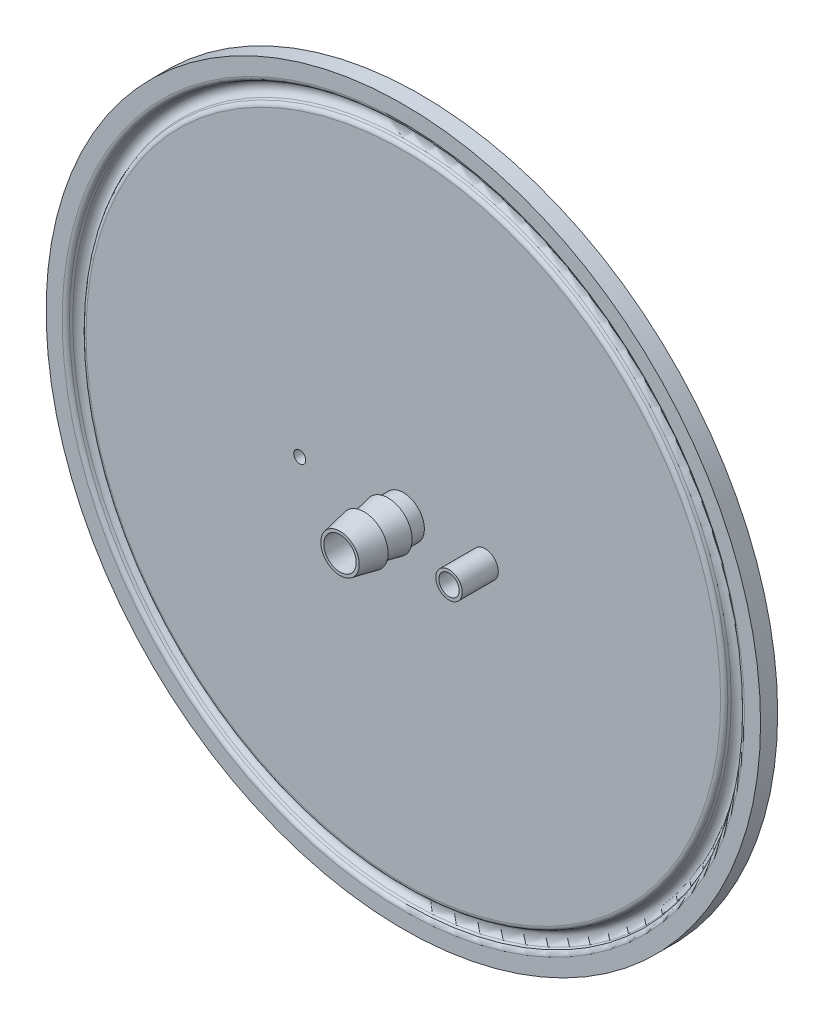
SolidWorks part; units mm, degrees
ref_plane "Front Plane" through (0, 0, 0) normal (0, 0, 1) x (1, 0, 0)
ref_plane "Top Plane" through (0, 0, 0) normal (0, 1, 0) x (1, 0, 0)
ref_plane "Right Plane" through (0, 0, 0) normal (1, 0, 0) x (0, 0, -1)
sketch "Sketch1" plane through (0, 0, 0) normal (1, 0, 0) x (0, 0, -1)
  line L0 (0, 0) -> (7.9248, 0) construction
  line L1 (0, 0) -> (0, 52.8099)
  line L2 (0, 59.4614) -> (2.8448, 59.4614)
  line L3 (2.8448, 59.4614) -> (7.9248, 45.5042)
  line L4 (7.9248, 45.5042) -> (7.9248, 0)
  line L5 (0, 56.7911) -> (0, 59.4614)
  line L6 (0.4797, 56.0663) -> (0.8729, 55.8994)
  line L7 (0.4797, 53.5347) -> (0.8729, 53.7016)
  line L8 (0, 56.2699) -> (0, 53.3311) construction
  line L9 (0, 54.8005) -> (0.4064, 54.8005) construction
  line L10 (0, 0) -> (7.9248, 0)
  arc A0 (0.8729, 53.7016) -> (0.8729, 55.8994) centre (0.4064, 54.8005) ccw
  arc A2 (0, 52.8099) -> (0.4797, 53.5347) centre (0.7874, 52.8099) cw
  arc A3 (0, 56.7911) -> (0.4797, 56.0663) centre (0.7874, 56.7911) ccw
  dimension "K" = 1.1938
  dimension "L" = 0.7874
  dimension "I" = 20
  dimension "C" = 91.0084
  dimension "F" = 2.8448
  dimension "H" = 0.4064
  dimension "B" = 109.601
  dimension "A" = 118.9228
  dimension "M" = 46
  dimension "N" = 23
  dimension "Length" = 7.9248
revolve "Revolve1" add sketch "Sketch1" angle 360 about L0
sketch "Sketch2" plane through (0, 0, -7.9248) normal (0, 0, -1) x (-1, 0, 0)
  circle A0 centre (-13.6038, 0) radius 2.2
  circle A1 centre (-13.6038, 0) radius 1.7
  dimension "D1" = 4.4
  dimension "D2" = 3.4
extrude "Boss-Extrude1" add sketch "Sketch2" along normal blind 6 separate body
sketch "Sketch3" plane through (0, 0, -7.9248) normal (0, 0, -1) x (-1, 0, 0)
  circle A0 centre (0, 0) radius 3.5
  dimension "D1" = 7
extrude "Boss-Extrude2" add sketch "Sketch3" along normal blind 2.54 separate body contours A0
sketch "Sketch4" plane through (0, 0, -10.4648) normal (0, 0, -1) x (-1, 0, 0)
  circle A0 centre (0, 0) radius 4
  dimension "D1" = 8
ref_plane "Plane1" through (0, 0, -14.4648) normal (0, 0, -1) x (-1, 0, 0)
sketch "Sketch6" plane through (0, 0, -14.4648) normal (0, 0, -1) x (-1, 0, 0)
  circle A0 centre (0, 0) radius 3.2
  dimension "D1" = 6.4
loft "Loft1" add profiles "Sketch6", "Sketch4" connector at (1.934, -2.5495, -14.4648) connector at (3.0203, -2.6225, -10.4648)
ref_plane "Plane2" through (0, 0, -18.4648) normal (0, 0, -1) x (-1, 0, 0)
sketch "Sketch7" plane through (0, 0, -14.4648) normal (0, 0, -1) x (-1, 0, 0)
  circle A0 centre (0, 0) radius 4
  dimension "D1" = 8
sketch "Sketch9" plane through (0, 0, -18.4648) normal (0, 0, -1) x (-1, 0, 0)
  circle A0 centre (0, 0) radius 3.2
  dimension "D1" = 6.4
loft "Loft2" add profiles "Sketch9", "Sketch7" connector at (3.1438, 0.5969, -18.4648) connector at (3.5954, 1.753, -14.4648)
ref_plane "Plane3" through (0, 0, -3.9624) normal (0, 0, -1) x (-1, 0, 0)
mirror "Mirror1" about plane through (0, 0, -3.9624) normal (0, 0, -1) of bodies 108 112
sketch "Sketch10" plane through (0, 0, -18.4648) normal (0, 0, -1) x (-1, 0, 0)
  circle A0 centre (0, 0) radius 2.7
  dimension "D1" = 5.4
extrude "Cut-Extrude1" cut sketch "Sketch10" against normal through all
sketch "Sketch11" plane through (0, 0, -7.9248) normal (0, 0, -1) x (-1, 0, 0)
  circle A0 centre (-13.6038, 0) radius 1.7
extrude "Cut-Extrude2" cut sketch "Sketch11" against normal up to surface (7.9248 mm away) up to face at (-2.7, 0, 0)
sketch "Sketch12" plane through (0, 0, -7.9248) normal (0, 0, -1) x (-1, 0, 0)
  circle A0 centre (17.2485, 0) radius 1
  circle A1 centre (17.2485, 0) radius 1.5
  dimension "D1" = 2
  dimension "D2" = 3
extrude "Boss-Extrude3" add sketch "Sketch12" along normal blind 2
sketch "Sketch13" plane through (0, 0, -7.9248) normal (0, 0, -1) x (-1, 0, 0)
  circle A0 centre (17.2485, 0) radius 1
extrude "Cut-Extrude3" cut sketch "Sketch13" against normal through all
